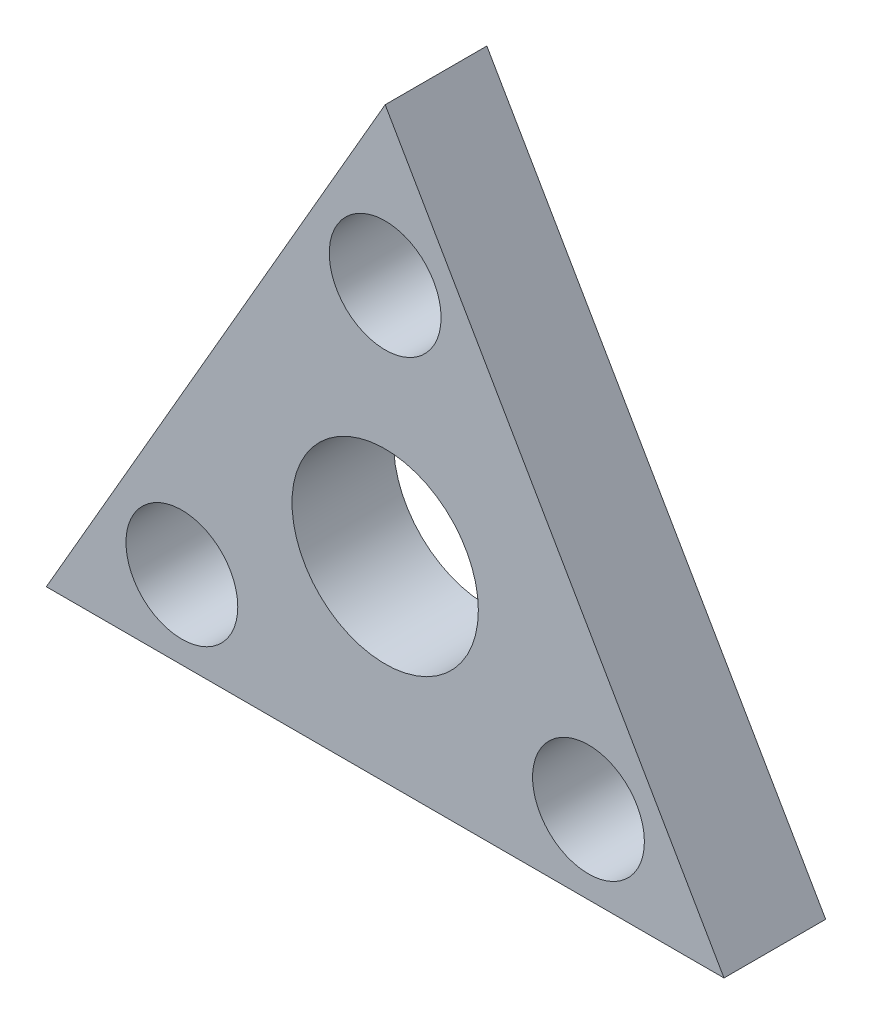
SolidWorks part; units mm, degrees
ref_plane "前视基准面" through (0, 0, 0) normal (0, 0, 1) x (1, 0, 0)
ref_plane "上视基准面" through (0, 0, 0) normal (0, 1, 0) x (1, 0, 0)
ref_plane "右视基准面" through (0, 0, 0) normal (1, 0, 0) x (0, 0, -1)
other "Configuration Table"
sketch "草图1" plane through (0, 0, 0) normal (0, 0, 1) x (1, 0, 0)
  line L1 (0, 11.547) -> (-10, -5.7735)
  line L2 (-10, -5.7735) -> (10, -5.7735)
  line L3 (10, -5.7735) -> (0, 11.547)
  line L4 (0, 6.9282) -> (-6, -3.4641) construction
  line L5 (-6, -3.4641) -> (6, -3.4641) construction
  line L6 (6, -3.4641) -> (0, 6.9282) construction
  circle A0 centre (0, 0) radius 5.7735 construction
  circle A1 centre (0, 0) radius 3.4641 construction
  circle A2 centre (0, 6.9282) radius 1.65
  circle A3 centre (-6, -3.4641) radius 1.65
  circle A4 centre (6, -3.4641) radius 1.65
  circle A5 centre (0, 0) radius 2.75
  dimension "D3" = 3.3
  dimension "D4" = 5.5
  dimension "D1" = 20
  dimension "D2" = 12
extrude "凸台-拉伸1" add sketch "草图1" along normal blind 3
